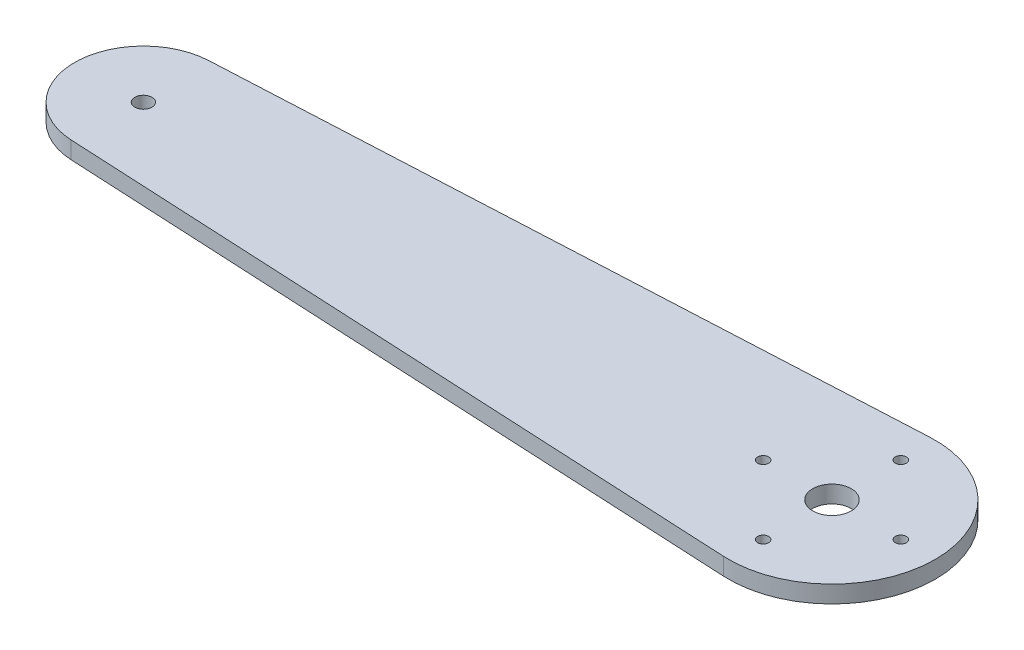
SolidWorks part; units mm, degrees
ref_plane "Front Plane" through (0, 0, 0) normal (0, 0, 1) x (1, 0, 0)
ref_plane "Top Plane" through (0, 0, 0) normal (0, 1, 0) x (1, 0, 0)
ref_plane "Right Plane" through (0, 0, 0) normal (1, 0, 0) x (0, 0, -1)
sketch "Sketch1" plane through (0, 0, 0) normal (0, 1, 0) x (1, 0, 0)
  line L0 (-127.635, 12.6841) -> (-0.9525, 19.0262)
  line L1 (-127.635, -12.6841) -> (-0.9525, -19.0262)
  line L2 (-111.3601, 0) -> (-50111.3601, 0) construction
  line L3 (0, -984.3615) -> (0, 49015.6385) construction
  line L4 (0, 0) -> (0, 12.7) construction
  line L5 (0, 0) -> (12.7, 0) construction
  arc A0 (-0.9525, -19.0262) -> (-0.9525, 19.0262) centre (0, 0) ccw
  arc A1 (-127.635, 12.6841) -> (-127.635, -12.6841) centre (-127, 0) ccw
  circle A2 centre (-127, 0) radius 1.5875
  circle A3 centre (0, 0) radius 3.556
  circle A4 centre (0, 12.7) radius 1.016
  circle A5 centre (12.7, 0) radius 1.016
  circle A6 centre (0, -12.7) radius 1.016
  circle A7 centre (-12.7, 0) radius 1.016
  dimension "D1" = 12.7
  dimension "D2" = 19.05
  dimension "D4" = 3.175
  dimension "D5" = 7.112
  dimension "D6" = 2.032
  dimension "D3" = 127
  dimension "D7" = 12.7
  dimension "D9" = 90
  dimension "D10" = 12.7
  dimension "D8" = 4
extrude "Boss-Extrude1" add sketch "Sketch1" along normal blind 3.175
